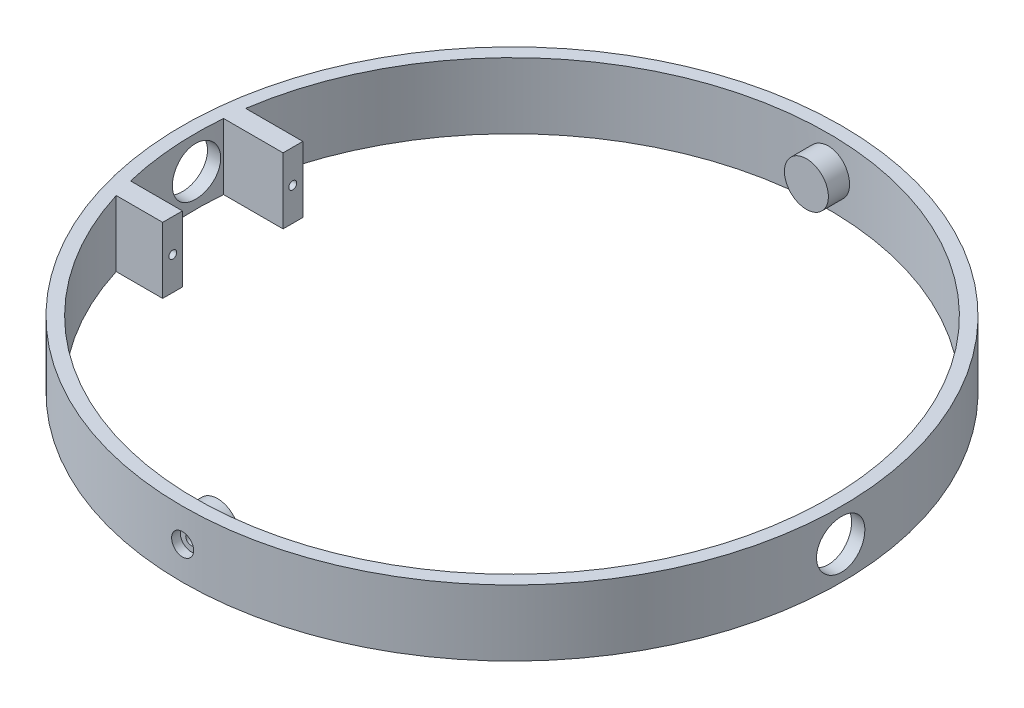
SolidWorks part; units mm, degrees
ref_plane "Front Plane" through (0, 0, 0) normal (0, 0, 1) x (1, 0, 0)
ref_plane "Top Plane" through (0, 0, 0) normal (0, 1, 0) x (1, 0, 0)
ref_plane "Right Plane" through (0, 0, 0) normal (1, 0, 0) x (0, 0, -1)
sketch "Sketch1" plane through (0, 0, 0) normal (0, 1, 0) x (1, 0, 0)
  circle A0 centre (0, 0) radius 72
  circle A1 centre (0, 0) radius 75
  dimension "D1" = 150
  dimension "D2" = 3
extrude "Boss-Extrude1" add sketch "Sketch1" along normal blind 15
sketch "Sketch2" plane through (0, 0, 0) normal (1, 0, 0) x (0, 0, -1)
  circle A0 centre (0, 7.5) radius 5.5
  dimension "D1" = 11
  dimension "D2" = 7.5
extrude "Cut-Extrude1" cut sketch "Sketch2" against normal through all and the other way through all
ref_plane "Plane1" through (0, 0, 73) normal (0, 0, 1) x (1, 0, 0)
sketch "Sketch3" plane through (0, 0, 73) normal (0, 0, 1) x (1, 0, 0)
  circle A0 centre (0, 7.5) radius 5
  point P2 (0, 0)
  dimension "D1" = 10
  dimension "D2" = 7.5
extrude "Boss-Extrude2" add sketch "Sketch3" along normal blind 1 and the other way blind 6 contours A0
mirror "Mirror1" about plane through (0, 0, 0) normal (0, 0, 1) of "Boss-Extrude2"
sketch "Sketch4" plane through (0, 15, 0) normal (0, 1, 0) x (1, 0, 0)
  line L0 (-58.2, -16.8) -> (-70.0126, -16.8)
  line L1 (-58.2, -16.8) -> (-58.2, -21.3)
  line L2 (-58.2, -21.3) -> (-70.0126, -21.3)
  line L3 (-70.0126, -21.3) -> (-70.0126, -16.8)
  line L4 (-58.2, 6.1) -> (-58.2, 10.6)
  line L5 (-58.2, 6.1) -> (-71.7411, 6.1)
  line L6 (-71.7411, 6.1) -> (-71.7411, 10.6)
  line L7 (-71.7411, 10.6) -> (-58.2, 10.6)
  circle A0 centre (0, 0) radius 72 construction
  point P11 (0, 0)
  point P14 (0, 0)
  point P15 (0, 0)
  point P17 (0, 0)
  point P18 (0, 0)
  point P19 (0, 0)
  dimension "D2" = 4.5
  dimension "D3" = 4.5
extrude "Boss-Extrude3" add sketch "Sketch4" against normal up to surface (15 mm away) up to face at (0, 0, 75)
sketch "Sketch5" plane through (-58.2, 0, 0) normal (1, 0, 0) x (0, 0, -1)
  circle A0 centre (8.3, 7.5) radius 0.9
  circle A1 centre (-19, 7.5) radius 0.9
  dimension "D1" = 1.8
  dimension "D2" = 1.8
extrude "Cut-Extrude2" cut sketch "Sketch5" against normal blind 8
sketch "Sketch6" plane through (0, 0, 67) normal (0, 0, -1) x (-1, 0, 0)
  circle A0 centre (0, 7.5) radius 2.45
  dimension "D1" = 4.9
extrude "Cut-Extrude3" cut sketch "Sketch6" against normal blind 4
sketch "Sketch7" plane through (0, 0, 71) normal (0, 0, -1) x (-1, 0, 0)
  circle A0 centre (0, 7.5) radius 1.25
  dimension "D1" = 2.5
extrude "Cut-Extrude4" cut sketch "Sketch7" against normal blind 4
ref_plane "Plane2" through (0, 0, 73) normal (0, 0, -1) x (-1, 0, 0)
sketch "Sketch8" plane through (0, 0, 73) normal (0, 0, -1) x (-1, 0, 0)
  circle A0 centre (0, 7.5) radius 2.5
  dimension "D1" = 5
extrude "Cut-Extrude5" cut sketch "Sketch8" against normal blind 4
